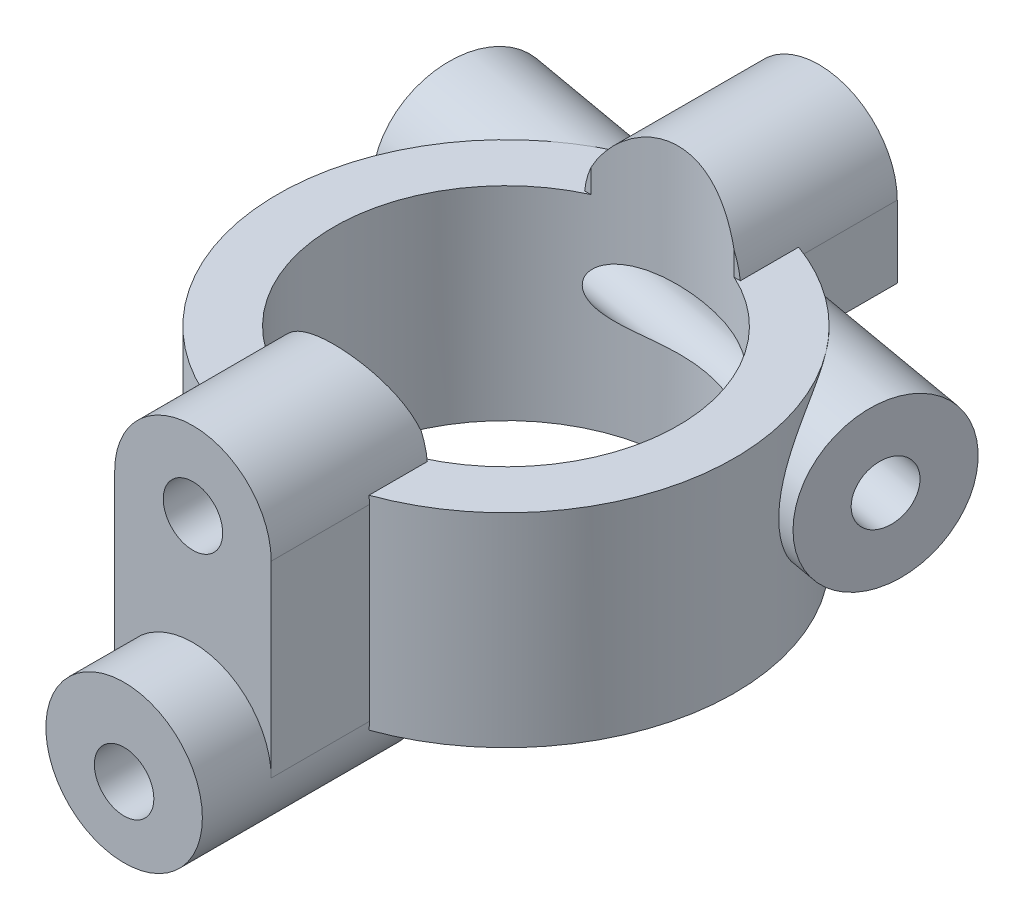
SolidWorks part; units mm, degrees
ref_plane "Front Plane" through (0, 0, 0) normal (0, 0, 1) x (1, 0, 0)
ref_plane "Top Plane" through (0, 0, 0) normal (0, 1, 0) x (1, 0, 0)
ref_plane "Right Plane" through (0, 0, 0) normal (1, 0, 0) x (0, 0, -1)
sketch "Sketch1" plane through (0, 0, 0) normal (0, 1, 0) x (1, 0, 0)
  circle A0 centre (0, 0) radius 9.271
  dimension "D2" = 18.542
extrude "Boss-Extrude1" add sketch "Sketch1" along normal blind 8.255
ref_plane "Plane1" through (0, 0, 6.35) normal (0, 0, 1) x (1, 0, 0)
ref_plane "Plane2" through (0, 0, -6.35) normal (0, 0, 1) x (1, 0, 0)
sketch "Sketch2" plane through (0, 0, 6.35) normal (0, 0, 1) x (1, 0, 0)
  line L0 (0, 8.255) -> (0, 0) construction
  line L2 (-6.985, 4.1275) -> (6.985, 4.1275) construction
  line L3 (9.271, 8.255) -> (-9.271, 8.255) construction
  line L5 (0, -2.8575) -> (0, 11.1125) construction
  line L7 (3.175, 0.3175) -> (3.175, 7.9375)
  line L9 (-3.175, 0.3175) -> (-3.175, 7.9375)
  line L10 (3.175, 0.3175) -> (-3.175, 7.9375) construction
  line L11 (3.175, 7.9375) -> (-3.175, 0.3175) construction
  arc A0 (-3.175, 7.9375) -> (3.175, 7.9375) centre (0, 7.9375) cw
  arc A1 (-3.175, 0.3175) -> (3.175, 0.3175) centre (0, 0.3175) ccw
  point P11 (0, 4.1275)
  dimension "D2" = 13.97
  dimension "D4" = 6.985
  dimension "D5" = 3.175
  dimension "D6" = 3.175
  dimension "D1" = 6.35
  dimension "D3" = 3.175
extrude "Boss-Extrude2" add sketch "Sketch2" along normal blind 6.35
sketch "Sketch7" plane through (0, 0, -6.35) normal (0, 0, 1) x (1, 0, 0)
  line L0 (-9.271, 0) -> (9.271, 0) construction
  line L2 (3.175, 7.9248) -> (3.175, 5.0038)
  line L3 (-3.175, 7.9248) -> (-3.175, 5.0038)
  line L4 (3.175, 5.0038) -> (1.2443, 5.0038)
  line L5 (-1.2443, 5.0038) -> (-3.175, 5.0038)
  arc A0 (3.175, 7.9248) -> (-3.175, 7.9248) centre (0, 7.9248) ccw
  arc A1 (1.2443, 5.0038) -> (-1.2443, 5.0038) centre (0, 7.9248) cw
  dimension "D3" = 3.175
  dimension "D4" = 3.175
  dimension "D1" = 7.9248
  dimension "D2" = 6.35
  dimension "D6" = 5.0038
  dimension "D7" = 1.9147
extrude "Boss-Extrude4" add sketch "Sketch7" against normal blind 6.35
sketch "Sketch4" plane through (0, 0, 12.7) normal (0, 0, 1) x (1, 0, 0)
  circle A0 centre (0, 0.3175) radius 3.175
  arc A1 (-3.175, 0.3175) -> (3.175, 0.3175) centre (0, 0.3175) ccw construction
  dimension "D1" = 6.35
extrude "Boss-Extrude3" add sketch "Sketch4" along normal blind 2.794
sketch "Sketch5" plane through (0, 0, 12.7) normal (0, 0, 1) x (1, 0, 0)
  circle A0 centre (0, 7.9375) radius 1.2065
  dimension "D1" = 2.413
sketch "Sketch6" plane through (0, 0, 15.494) normal (0, 0, 1) x (1, 0, 0)
  circle A0 centre (0, 0) radius 1.2065
  dimension "D1" = 2.413
ref_plane "Plane3" through (-9.1302, 0, -1.6099) normal (-0.9848, 0, -0.1736) x (-0.1736, 0, 0.9848)
sketch "Sketch9" plane through (-9.1302, 0, -1.6099) normal (-0.9848, 0, -0.1736) x (-0.1736, 0, 0.9848)
  line L1 (9.1323, 8.255) -> (-8.0359, 8.255) construction
  circle A0 centre (-6.8033, 5.0122) radius 3.2428
  dimension "D1" = 6.4855
  dimension "D2" = 5.1524
extrude "Boss-Extrude5" add sketch "Sketch9" against normal blind 18.542 and the other way blind 2.5019
sketch "Sketch11" plane through (0, 8.255, 0) normal (0, 1, 0) x (1, 0, 0)
  circle A0 centre (0, 0) radius 6.985
  dimension "D1" = 13.97
extrude "Cut-Extrude9" cut sketch "Sketch11" against normal blind 19.304 and the other way blind 19.304
extrude "Cut-Extrude10" cut sketch "Sketch6" against normal up to next
sketch "Sketch12" plane through (-11.594, 0, -2.0443) normal (-0.9848, 0, -0.1736) x (-0.1736, 0, 0.9848)
  circle A0 centre (-6.8033, 5.0122) radius 1.2065
  dimension "D1" = 2.413
extrude "Cut-Extrude11" cut sketch "Sketch12" against normal through all
extrude "Cut-Extrude12" cut sketch "Sketch5" against normal blind 3.81
mirror "Mirror2" about plane through (0, 0, 0) normal (0, 0, 1) of "Cut-Extrude12"
